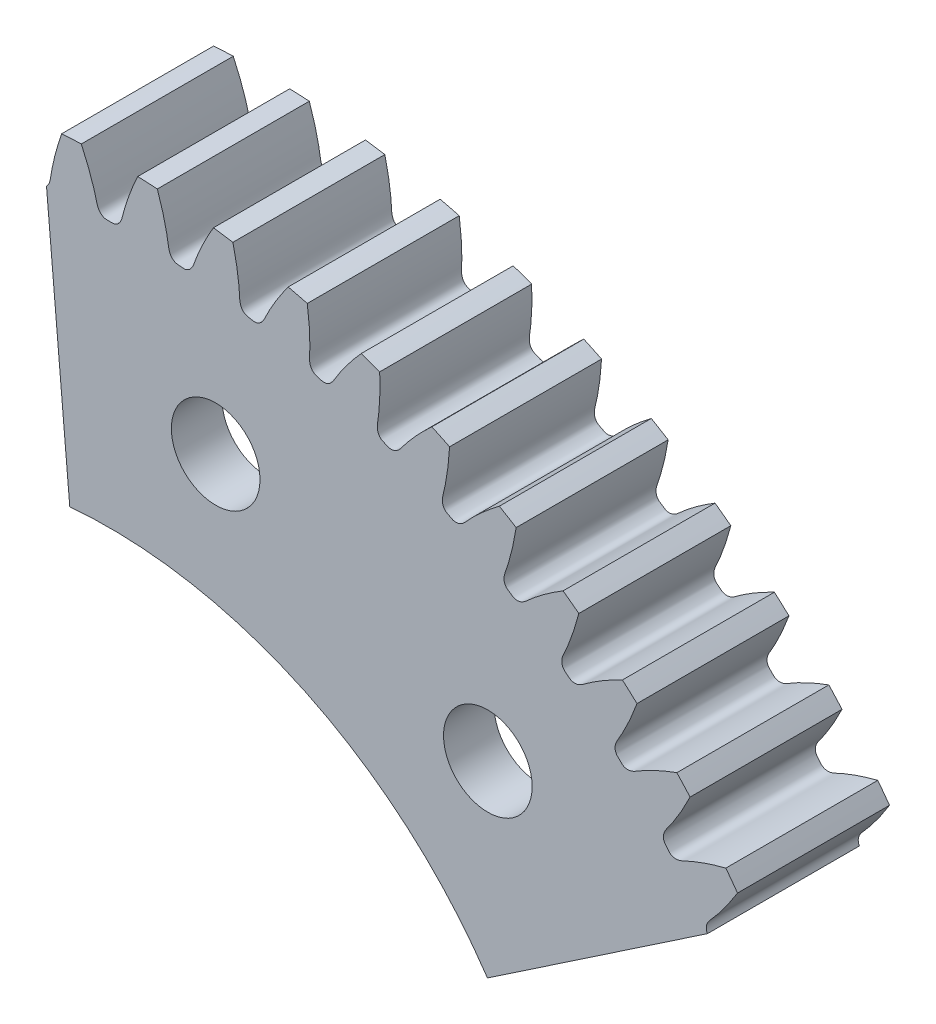
SolidWorks part; units mm, degrees
material "Д16 ГОСТ 4784-97"
ref_plane "FRONT" through (0, 0, 0) normal (0, 0, 1) x (1, 0, 0)
ref_plane "TOP" through (0, 0, 0) normal (0, 1, 0) x (1, 0, 0)
ref_plane "RIGHT" through (0, 0, 0) normal (1, 0, 0) x (0, 0, -1)
ref_axis "Ось1" through (0, 0, 50) along (0, 0, -1)
sketch "SketchRevolveSpurAssemblyNew1Gear" plane through (0, 0, 0) normal (1, 0, 0) x (0, 0, -1)
  line L0 (0, 0) -> (1, 0) construction
  line L1 (-4, 0) -> (-4, 30.5859)
  line L2 (-4, 30.5859) -> (2, 30.5859)
  line L3 (2, 30.5859) -> (2, 0)
  line L4 (2, 0) -> (-4, 0)
  dimension "D1" = 6
revolve "SpurAssemblyNew1Gear" add sketch "SketchRevolveSpurAssemblyNew1Gear" angle 360 about L0
sketch "SketchToothSpurAssemblyNew1Gear" plane through (0, 0, 0) normal (0, 0, 1) x (1, 0, 0)
  arc A0 (30.5945, 1.1268) -> (30.5945, -1.1268) centre (0, 0) cw
  spline S0 degree 3 poles (30.5945, -1.1268) (30.5132, -1.0888) (30.3922, -1.0339) (30.2321, -0.9645) (30.1166, -0.9161) (30.0041, -0.8705) (29.8946, -0.8275) (29.7881, -0.7872) (29.6848, -0.7494) (29.5845, -0.7141) (29.4875, -0.6811) (29.3937, -0.6505) (29.3032, -0.6221) (29.216, -0.5958) (29.1321, -0.5716) (29.0516, -0.5494) (28.953, -0.523) (28.873, -0.505) (28.8129, -0.4861) (28.7913, -0.4788) (28.7701, -0.4709) (28.7493, -0.4625) (28.7287, -0.4535) (28.7084, -0.4437) (28.6882, -0.4331) (28.6681, -0.4215) (28.648, -0.4087) (28.6279, -0.3944) (28.6078, -0.3785) (28.5876, -0.3604) (28.5676, -0.3397) (28.5479, -0.3161) (28.529, -0.289) (28.5115, -0.2581) (28.4964, -0.2233) (28.4848, -0.1848) (28.478, -0.1456) (28.4749, -0.0836) (28.4778, 0) (28.4749, 0.0836) (28.478, 0.1456) (28.4848, 0.1848) (28.4964, 0.2233) (28.5115, 0.2581) (28.529, 0.289) (28.5479, 0.3161) (28.5676, 0.3397) (28.5876, 0.3604) (28.6078, 0.3785) (28.6279, 0.3944) (28.648, 0.4087) (28.6681, 0.4215) (28.6882, 0.4331) (28.7084, 0.4437) (28.7287, 0.4535) (28.7493, 0.4625) (28.7701, 0.4709) (28.7913, 0.4788) (28.8129, 0.4861) (28.873, 0.505) (28.953, 0.523) (29.0516, 0.5494) (29.1321, 0.5716) (29.216, 0.5958) (29.3032, 0.6221) (29.3937, 0.6505) (29.4875, 0.6811) (29.5845, 0.7141) (29.6848, 0.7494) (29.7881, 0.7872) (29.8946, 0.8275) (30.0041, 0.8705) (30.1166, 0.9161) (30.2321, 0.9645) (30.3922, 1.0339) (30.5132, 1.0888) (30.5945, 1.1268) knots 0 0 0 0 0.052869 0.078188 0.102762 0.126592 0.149678 0.172019 0.193617 0.21447 0.234579 0.253943 0.272564 0.29044 0.307572 0.32396 0.339603 0.367681 0.372205 0.376674 0.381103 0.385507 0.389906 0.394324 0.398788 0.403329 0.407986 0.412802 0.417828 0.423121 0.428742 0.434755 0.441216 0.448165 0.45561 0.463513 0.471776 0.478976 0.5 0.521024 0.528224 0.536487 0.54439 0.551835 0.558784 0.565245 0.571258 0.576879 0.582172 0.587198 0.592014 0.596671 0.601212 0.605676 0.610094 0.614493 0.618897 0.623326 0.627795 0.632319 0.660397 0.67604 0.692428 0.70956 0.727436 0.746057 0.765421 0.78553 0.806383 0.827981 0.850322 0.873408 0.897238 0.921812 0.947131 1 1 1 1
extrude "ToothExtrudeCutSpurAssemblyNew1Gear" cut sketch "SketchToothSpurAssemblyNew1Gear" against normal blind 4 and the other way blind 4
pattern_circular "PatternSpurAssemblyNew1Gear" count 64 every 5.625 about axis through (0, 0, 50) along (0, 0, -1) of "ToothExtrudeCutSpurAssemblyNew1Gear"
sketch "AuxiliarySketchSpurAssemblyNew1Gear" plane through (0, 0, 0) normal (0, 0, 1) x (1, 0, 0)
  circle A0 centre (0, 0) radius 30 construction
  circle A1 centre (0, 0) radius 28.1908 construction
  circle A2 centre (0, 0) radius 28.8965 construction
  circle A3 centre (0, 0) radius 30.5859 construction
  circle A4 centre (0, 0) radius 28.4766 construction
  dimension "PitchDiameter" = 60
  dimension "BaseDiameter" = 56.3816
  dimension "FormDiameter" = 57.7931
  dimension "MajorDiameter" = 61.1719
  dimension "MinorDiameter" = 56.9531
sketch "Эскиз1" plane through (0, 0, 4) normal (0, 0, 1) x (1, 0, 0)
  line L0 (0, 0) -> (-2.8174, 32.2029) construction
  line L1 (0, 0) -> (26.7994, 18.0764) construction
  line L2 (0, 0) -> (4.1914, 22.6149) construction
  line L4 (-1.5688, 17.9315) -> (-2.8174, 32.2029)
  line L5 (14.9227, 10.0655) -> (26.7994, 18.0764)
  line L6 (0, 0) -> (0, 30.5657) construction
  line L7 (0, 0) -> (9.9018, 20.7595) construction
  arc A0 (-2.8174, 32.2029) -> (26.7994, 18.0764) centre (0, 0) ccw
  arc A1 (19.0679, 12.8614) -> (-2.0046, 22.9125) centre (0, 0) ccw construction
  circle A2 centre (4.1914, 22.6149) radius 1.75
  circle A3 centre (14.9373, 17.4893) radius 1.75
  arc A4 (14.9227, 10.0655) -> (-1.5688, 17.9315) centre (0, 0) ccw
  point P1 (6.0154, 22.9125)
  point P9 (5.2313, 21.7901)
  point P10 (0, 30.5657)
  dimension "D1" = 61
  dimension "D2" = 15
  dimension "D3" = 23
  dimension "D4" = 3.5
  dimension "D7" = 18
  dimension "D8" = 5
extrude "Отсечение части и крепежные отверстия" cut sketch "Эскиз1" against normal through all
sketch "Эскиз2" plane through (0, 0, -2) normal (0, 0, 1) x (1, 0, 0)
  circle A0 centre (0, 0) radius 26.5
  dimension "D1" = 53
extrude "Вырез под плстину" cut sketch "Эскиз2" along normal blind 4
